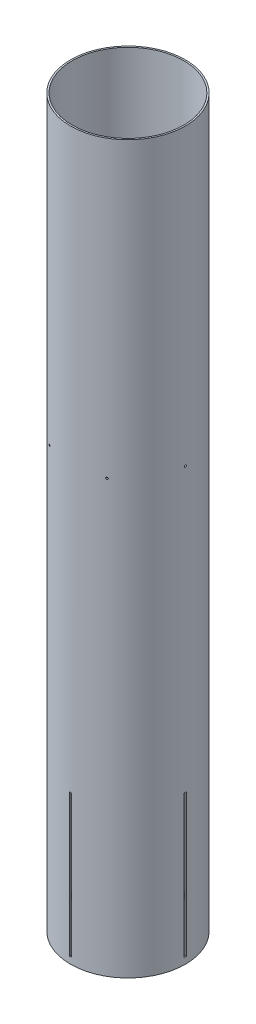
SolidWorks part; units mm, degrees
material "A-Glass Fiber"
ref_plane "Front Plane" through (0, 0, 0) normal (0, 0, 1) x (1, 0, 0)
ref_plane "Top Plane" through (0, 0, 0) normal (0, 1, 0) x (1, 0, 0)
ref_plane "Right Plane" through (0, 0, 0) normal (1, 0, 0) x (0, 0, -1)
sketch "Sketch1" plane through (0, 0, 0) normal (0, 1, 0) x (1, 0, 0)
  circle A0 centre (0, 0) radius 76.2
  circle A1 centre (0, 0) radius 78.359
  dimension "D1" = 152.4
  dimension "D2" = 156.718
extrude "Boss-Extrude1" add sketch "Sketch1" along normal blind 990.6
ref_plane "Plane1" through (0, 0, 0) normal (0.7071, 0, 0.7071) x (0.7071, 0, -0.7071)
ref_axis "Axis1" through (0, 990.6, 0) along (0, -1, 0)
sketch "Sketch2" plane through (0, 0, 0) normal (1, 0, 0) x (0, 0, -1)
  line L0 (0, 0) -> (0, 8.89)
  line L1 (1.5875, 8.89) -> (-1.5875, 8.89)
  line L2 (1.5875, 8.89) -> (1.5875, 203.2)
  line L3 (1.5875, 203.2) -> (-1.5875, 203.2)
  line L4 (-1.5875, 8.89) -> (-1.5875, 203.2)
  line L5 (1.5875, 8.89) -> (-1.5875, 203.2) construction
  line L6 (1.5875, 203.2) -> (-1.5875, 8.89) construction
  line L7 (78.359, 990.6) -> (-78.359, 990.6) construction
  line L8 (78.359, 990.6) -> (-78.359, 990.6)
  line L9 (0, 990.6) -> (0, 588.645)
  line L10 (-78.359, 0) -> (78.359, 0) construction
  circle A0 centre (0, 588.645) radius 1.3525
  point P0 (0, 106.045)
  dimension "D4" = 2.7051
  dimension "D1" = 3.175
  dimension "D2" = 194.31
  dimension "D5" = 588.645
  dimension "D3" = 203.2
extrude "Cut-Extrude1" cut sketch "Sketch2" against normal through all contours L4 L1 L2 L3 region at (0, 106.045, 0)
pattern_circular "CirPattern1" count 4 over 360 about axis through (0, 0, 0) along (0, 1, 0) of "Cut-Extrude1" reverse direction yes
extrude "Cut-Extrude2" cut sketch "Sketch2<3>" against normal through all contours A0 region at (0, 587.7157, 0.9293)
sketch "Sketch2<3>" plane through (0, 0, 0) normal (1, 0, 0) x (0, 0, -1) same geometry as "Sketch2"
pattern_circular "CirPattern2" count 6 over 360 about axis through (0, 990.6, 0) along (0, -1, 0) of "Cut-Extrude2"
sketch "Sketch3" plane through (0, 0, 0) normal (0.7071, 0, 0.7071) x (0.7071, 0, -0.7071)
  line L0 (0, 0) -> (0, 127) construction
  circle A0 centre (0, 127) radius 3.175
  dimension "D1" = 6.35
  dimension "D2" = 127
extrude "Cut-Extrude3" cut sketch "Sketch3" against normal through all
equation "\"Aft_Lower_Length\"= 22in"
equation "\"D1@Boss-Extrude1\" = \"Aft_Section_Length\""
equation "\"AB_Coupler_OD_Length\"= 1in"
equation "\"AB_Coupling_Section_Length\"= 0.375in"
equation "\"AB_Coupler_Length\"= \"AB_Coupler_OD_Length\" + \"AB_Coupling_Section_Length\" * 2"
equation "\"AB_Coupler_Num_Screws\"= 6"
equation "\"AB_Coupling_Screw_Diameter\"= 0.1065in"
equation "\"Aft_Section_Length\"= 39in"
equation "\"D4@Sketch2\"=\"AB_Coupling_Screw_Diameter\""
equation "\"D1@CirPattern2\"=\"AB_Coupler_Num_Screws\""
equation "\"Rail_Nut_From_Bottom\"= 5in"
equation "\"Rail_Nut_Diam\"= 0.25in"
equation "\"D1@Sketch3\"=\"Rail_Nut_Diam\""
equation "\"D2@Sketch3\"=\"Rail_Nut_From_Bottom\""
